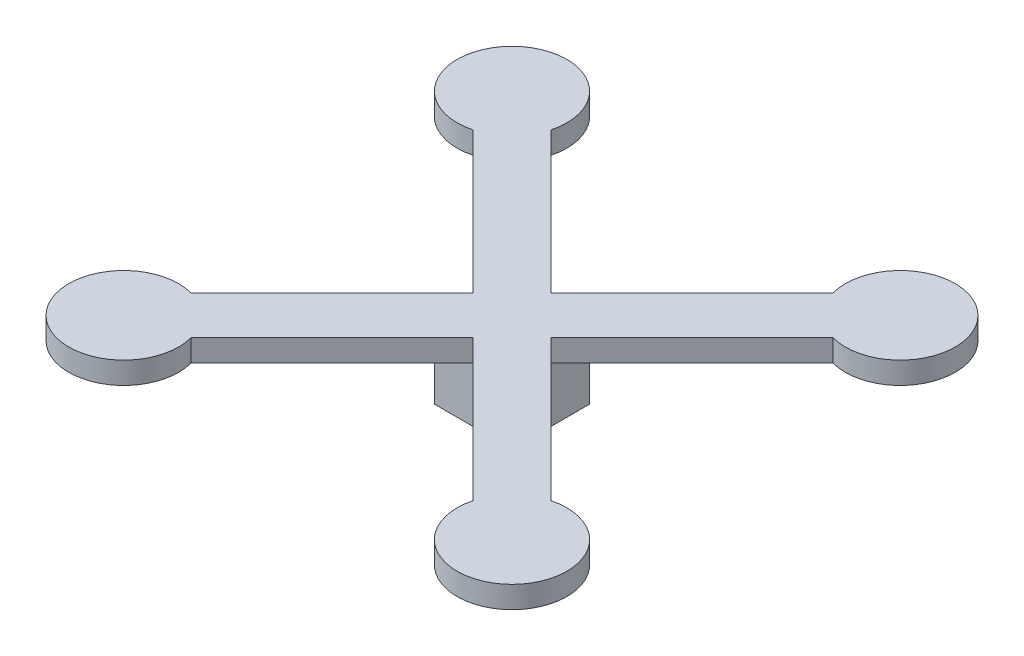
SolidWorks part; units mm, degrees
ref_plane "Front Plane" through (0, 0, 0) normal (0, 0, 1) x (1, 0, 0)
ref_plane "Top Plane" through (0, 0, 0) normal (0, 1, 0) x (1, 0, 0)
ref_plane "Right Plane" through (0, 0, 0) normal (1, 0, 0) x (0, 0, -1)
sketch "Sketch1" plane through (0, 0, 0) normal (0, 1, 0) x (1, 0, 0)
  line L0 (-17.6777, 17.6777) -> (17.6777, -17.6777)
  line L1 (17.6777, -17.6777) -> (194.4544, 159.099)
  line L2 (194.4544, 159.099) -> (159.099, 194.4544)
  line L3 (159.099, 194.4544) -> (-17.6777, 17.6777)
  line L4 (0, 0) -> (-70.3293, 0) construction
  line L5 (194.4544, -159.099) -> (17.6777, 17.6777)
  line L6 (17.6777, 17.6777) -> (-17.6777, -17.6777)
  line L7 (-17.6777, -17.6777) -> (159.099, -194.4544)
  line L8 (159.099, -194.4544) -> (194.4544, -159.099)
  line L9 (-159.099, -194.4544) -> (17.6777, -17.6777)
  line L10 (17.6777, -17.6777) -> (-17.6777, 17.6777)
  line L11 (-17.6777, 17.6777) -> (-194.4544, -159.099)
  line L12 (-194.4544, -159.099) -> (-159.099, -194.4544)
  line L13 (-194.4544, 159.099) -> (-17.6777, -17.6777)
  line L14 (-17.6777, -17.6777) -> (17.6777, 17.6777)
  line L15 (17.6777, 17.6777) -> (-159.099, 194.4544)
  line L16 (-159.099, 194.4544) -> (-194.4544, 159.099)
  circle A0 centre (176.7767, 176.7767) radius 50
  circle A1 centre (176.7767, -176.7767) radius 50
  circle A2 centre (-176.7767, -176.7767) radius 50
  circle A3 centre (-176.7767, 176.7767) radius 50
  point P4 (0, 0)
  point P31 (0, 0)
  dimension "D2" = 50
  dimension "D3" = 100
  dimension "D1" = 250
  dimension "D4" = 45
  dimension "D5" = 4
extrude "Boss-Extrude1" add sketch "Sketch1" along normal blind 20 contours L11 A2 L9 L12 | L9 A2 L11 L12 | A2 L9 L7 L13 L11 | L15 A3 L13 L16 | L13 A3 L15 L16 | A3 L13 L11 L3 L15 | A0 L3 L15 L5 L1 | L3 A0 L1 L2 | L1 A0 L3 L2 | A1 L5 L1 L9 L7 | L5 A1 L7 L8 | L7 A1 L5 L8 | L5 L6 L0 L1 | L7 L9 L0 L6 | L4 L0 L11 | L6 L15 L3 L0 | L6 L4 L13 region at (0, 0, -17.6777) region at (-80.3243, 0, -80.3243) region at (-17.6777, 0, -5.8926) region at (17.6777, 0, 0) region at (-17.6777, 0, 5.8926) region at (0, 0, 17.6777) region at (80.3243, 0, -80.3243) region at (-80.3243, 0, 80.3243) region at (80.3243, 0, 80.3243) region at (184.193, 0, -184.193) region at (159.8372, 0, -159.8372) region at (-159.8372, 0, -159.8372) region at (-184.193, 0, -184.193) region at (-159.8372, 0, 159.8372) region at (-184.193, 0, 184.193) region at (184.193, 0, 184.193) region at (159.8372, 0, 159.8372)
sketch "Sketch2" plane through (0, 0, 0) normal (0, -1, 0) x (1, 0, 0)
  line L1 (-35.3553, 35.3553) -> (35.3553, 35.3553)
  line L2 (-35.3553, 35.3553) -> (-35.3553, -35.3553)
  line L3 (-35.3553, -35.3553) -> (35.3553, -35.3553)
  line L4 (35.3553, 35.3553) -> (35.3553, -35.3553)
  line L5 (-35.3553, 35.3553) -> (35.3553, -35.3553) construction
  line L6 (-35.3553, -35.3553) -> (35.3553, 35.3553) construction
  point P0 (0, 0)
extrude "Boss-Extrude2" add sketch "Sketch2" along normal blind 50
